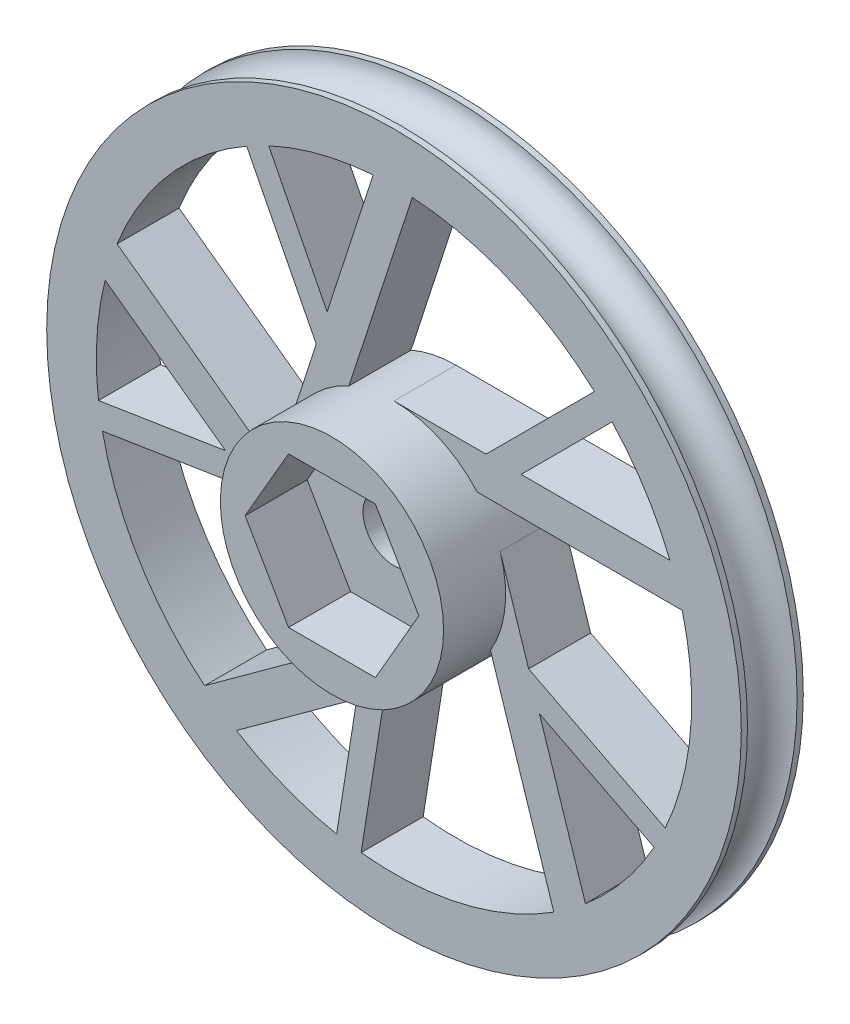
SolidWorks part; units mm, degrees
note: The reader was unsure of these and kept them because the rebuilt part matched: shared geometry of "草图1<3>".
ref_plane "前视基准面" through (0, 0, 0) normal (0, 0, 1) x (1, 0, 0)
ref_plane "上视基准面" through (0, 0, 0) normal (0, 1, 0) x (1, 0, 0)
ref_plane "右视基准面" through (0, 0, 0) normal (1, 0, 0) x (0, 0, -1)
sketch "草图1" plane through (0, 0, 0) normal (0, 0, 1) x (1, 0, 0)
  line L0 (0, 9) -> (22.2486, 9)
  line L1 (-3.5, 6.0622) -> (-7, 0)
  line L2 (-7, 0) -> (-3.5, -6.0622)
  line L3 (-3.5, -6.0622) -> (3.5, -6.0622)
  line L4 (3.5, -6.0622) -> (7, 0)
  line L5 (7, 0) -> (3.5, 6.0622)
  line L6 (3.5, 6.0622) -> (-3.5, 6.0622)
  line L7 (6.7082, 6) -> (23.2379, 6)
  line L8 (10.2486, 9) -> (17.5834, 16.3348)
  line L9 (7.4202, 9) -> (16.1623, 17.7421)
  line L10 (8.5595, 2.7812) -> (15.4347, -18.3785)
  line L11 (7.7793, -4.5258) -> (12.8872, -20.2465)
  line L12 (11.7265, -6.9658) -> (20.9689, -11.6751)
  line L13 (10.8525, -4.2758) -> (21.8681, -9.8886)
  line L14 (5.2901, -7.2812) -> (-12.7094, -20.3585)
  line L15 (-1.9003, -8.7971) -> (-15.2731, -18.513)
  line L16 (-3.0012, -13.3051) -> (-4.6239, -23.5504)
  line L17 (-0.713, -11.6426) -> (-2.647, -23.8536)
  line L18 (-5.2901, -7.2812) -> (-23.2896, 5.7962)
  line L19 (-8.9538, -0.9111) -> (-22.3266, 8.8048)
  line L20 (-13.5814, -1.2572) -> (-23.8266, -2.8799)
  line L21 (-11.2931, -2.9197) -> (-23.5041, -4.8537)
  line L22 (-8.5595, 2.7812) -> (-1.6843, 23.9408)
  line L23 (-3.6334, 8.234) -> (1.4746, 23.9547)
  line L24 (-5.3925, 12.5281) -> (-10.1017, 21.7705)
  line L25 (-6.2666, 9.8382) -> (-11.8793, 20.8538)
  line L26 (0, 0) -> (6.7082, 6) construction
  circle A0 centre (0, 0) radius 28
  circle A1 centre (0, 0) radius 9
  circle A2 centre (0, 0) radius 6.0622 construction
  circle A3 centre (0, 0) radius 24
  circle A4 centre (0, 0) radius 24
  circle A5 centre (0, 0) radius 24
  circle A6 centre (0, 0) radius 24
  circle A7 centre (0, 0) radius 24
  dimension "D1" = 56
  dimension "D2" = 18
  dimension "D4" = 48
  dimension "D3" = 7
  dimension "D5" = 3
  dimension "D6" = 45
  dimension "D7" = 2
  dimension "D8" = 12
  dimension "D9" = 5
extrude "凸台-拉伸1" add sketch "草图1" along normal blind 5 contours A0 A3 | L24 A3 L25 L22 | L23 A3 L22 A1 | L8 A3 L9 L0 | L7 A3 L0 A1 | L11 A3 L10 A1 | L12 A3 L13 L10 | L15 A3 L14 A1 | L16 A3 L17 L14 | L20 A3 L21 L18 | L19 A3 L18 A1 | L5 L6 L1 L2 L3 L4
extrude "凸台-拉伸2" add sketch "草图1<3>" along normal blind 10 contours A1 L6 L5 L4 L3 L2 L1
sketch "草图1<3>" plane through (0, 0, 0) normal (0, 0, 1) x (1, 0, 0) same geometry as "草图1"
sketch "草图2" plane through (0, 0, 0) normal (0, 0, -1) x (-1, 0, 0)
  circle A0 centre (0, 0) radius 2.5
  dimension "D1" = 5
extrude "切除-拉伸1" cut sketch "草图2" against normal through all
sketch "草图3" plane through (0, 0, 0) normal (0, 1, 0) x (1, 0, 0)
  line L0 (28, 0) -> (28, -5)
  line L1 (-28, -5) -> (-28, 0)
  line L2 (-28, -2.5) -> (0, -2.5) construction
  line L3 (28, 0) -> (28, -5)
  line L4 (0, 0) -> (0, -5) construction
  circle A0 centre (-28, -2.5) radius 2
  point P4 (-28, -2.5)
  dimension "D1" = 4
  dimension "D2" = 28
revolve "切除-旋转1" cut sketch "草图3" angle 360 about L4
